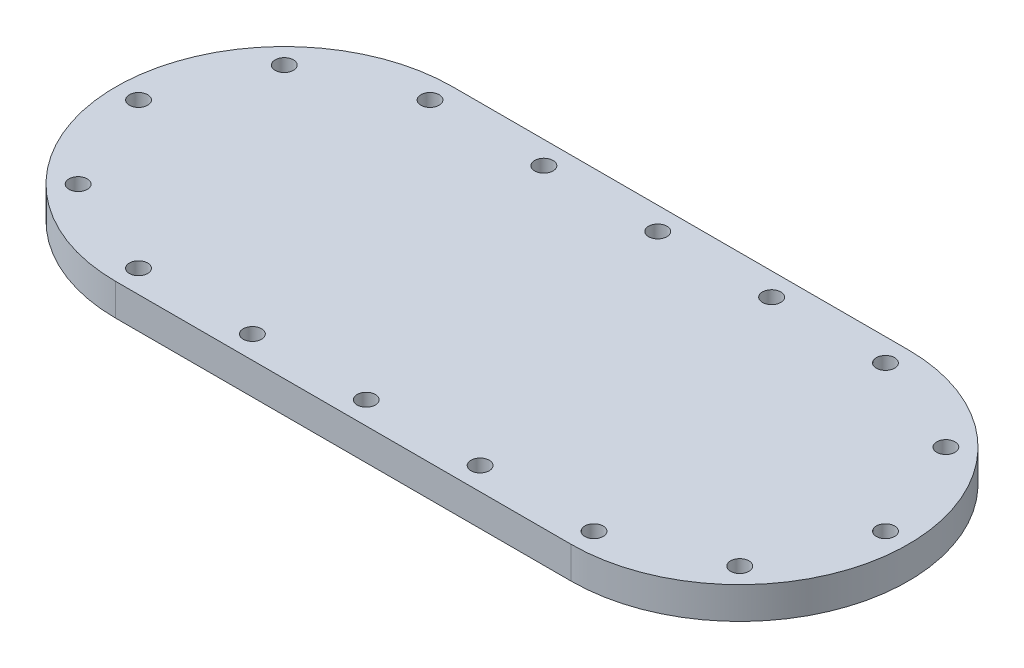
SolidWorks part; units mm, degrees
material "Acrylic (Medium-high impact)"
ref_plane "Front Plane" through (0, 0, 0) normal (0, 0, 1) x (1, 0, 0)
ref_plane "Top Plane" through (0, 0, 0) normal (0, 1, 0) x (1, 0, 0)
ref_plane "Right Plane" through (0, 0, 0) normal (1, 0, 0) x (0, 0, -1)
sketch "Sketch1" plane through (0, 0, 0) normal (0, 1, 0) x (1, 0, 0)
  line L0 (0, 46.99) -> (0, -46.99) construction
  line L3 (-63.5, 46.99) -> (63.5, 46.99)
  line L4 (-63.5, -46.99) -> (63.5, -46.99)
  line L5 (-63.5, 40.64) -> (63.5, 40.64) construction
  line L6 (-63.5, -40.64) -> (63.5, -40.64) construction
  arc A2 (63.5, -46.99) -> (63.5, 46.99) centre (63.5, 0) ccw
  arc A3 (-63.5, 46.99) -> (-63.5, -46.99) centre (-63.5, 0) ccw
  arc A4 (63.5, -40.64) -> (63.5, 40.64) centre (63.5, 0) ccw construction
  arc A5 (-63.5, 40.64) -> (-63.5, -40.64) centre (-63.5, 0) ccw construction
  circle A6 centre (-63.5, 40.64) radius 2.5527
  circle A7 centre (-31.75, 40.64) radius 2.5527
  circle A8 centre (0, 40.64) radius 2.5527
  circle A9 centre (31.75, 40.64) radius 2.5527
  circle A10 centre (63.5, 40.64) radius 2.5527
  circle A23 centre (92.2368, 28.7368) radius 2.5527
  circle A24 centre (104.14, 0) radius 2.5527
  circle A25 centre (92.2368, -28.7368) radius 2.5527
  circle A26 centre (63.5, -40.64) radius 2.5527
  circle A27 centre (-92.2368, 28.7368) radius 2.5527
  circle A28 centre (-104.14, 0) radius 2.5527
  circle A29 centre (-92.2368, -28.7368) radius 2.5527
  circle A30 centre (-63.5, -40.64) radius 2.5527
  circle A31 centre (31.75, -40.64) radius 2.5527
  circle A32 centre (0, -40.64) radius 2.5527
  circle A33 centre (-31.75, -40.64) radius 2.5527
  arc A34 (63.5, -40.64) -> (63.5, 40.64) centre (63.5, 0) ccw construction
  arc A35 (-63.5, 40.64) -> (-63.5, -40.64) centre (-63.5, 0) ccw construction
  point P42 (-63.5, 0)
  point P51 (-63.5, 0)
  point P53 (63.5, 0)
  dimension "D4" = 5
  dimension "1/4 - 20 bolt clearance" = 5.1054
  dimension "D5" = 5
  dimension "D1" = 127
  dimension "D2" = 93.98
  dimension "D3" = 6.35
  dimension "D7" = 4
  dimension "D6" = 5
extrude "Boss-Extrude1" add sketch "Sketch1" along normal blind 8.89 contours L3 A3 L4 A2 region at (0, 0, 0)
sketch "Sketch2" plane through (0, 0, 0) normal (0, -1, 0) x (1, 0, 0)
  line L0 (1.3877, 29.693) -> (65.9877, 29.693) construction
  line L1 (65.9877, 34.0618) -> (1.3877, 34.0618) construction
  line L2 (65.9877, -29.4382) -> (-63.2123, -29.4382) construction
  line L3 (-63.2123, -33.807) -> (65.9877, -33.807) construction
  line L4 (-63.2123, 29.693) -> (1.3877, 29.693) construction
  line L5 (1.3877, 34.0618) -> (-63.2123, 34.0618) construction
  line L6 (1.3877, 29.693) -> (65.9877, 29.693) construction
  line L7 (65.9877, 34.0618) -> (1.3877, 34.0618) construction
  line L8 (65.9877, -29.4382) -> (-63.2123, -29.4382) construction
  line L9 (-63.2123, -33.807) -> (65.9877, -33.807) construction
  line L10 (-63.2123, 29.693) -> (1.3877, 29.693) construction
  line L11 (1.3877, 34.0618) -> (-63.2123, 34.0618) construction
  arc A0 (65.9877, -29.4382) -> (65.9877, 29.693) centre (65.9877, 0.1274) ccw construction
  arc A1 (65.9877, -33.807) -> (65.9877, 34.0618) centre (65.9877, 0.1274) ccw construction
  arc A2 (-63.2123, 29.693) -> (-63.2123, -29.4382) centre (-63.2123, 0.1274) ccw construction
  arc A3 (-63.2123, 34.0618) -> (-63.2123, -33.807) centre (-63.2123, 0.1274) ccw construction
  arc A4 (65.9877, -29.4382) -> (65.9877, 29.693) centre (65.9877, 0.1274) ccw construction
  arc A5 (65.9877, -33.807) -> (65.9877, 34.0618) centre (65.9877, 0.1274) ccw construction
  arc A6 (-63.2123, 29.693) -> (-63.2123, -29.4382) centre (-63.2123, 0.1274) ccw construction
  arc A7 (-63.2123, 34.0618) -> (-63.2123, -33.807) centre (-63.2123, 0.1274) ccw construction
